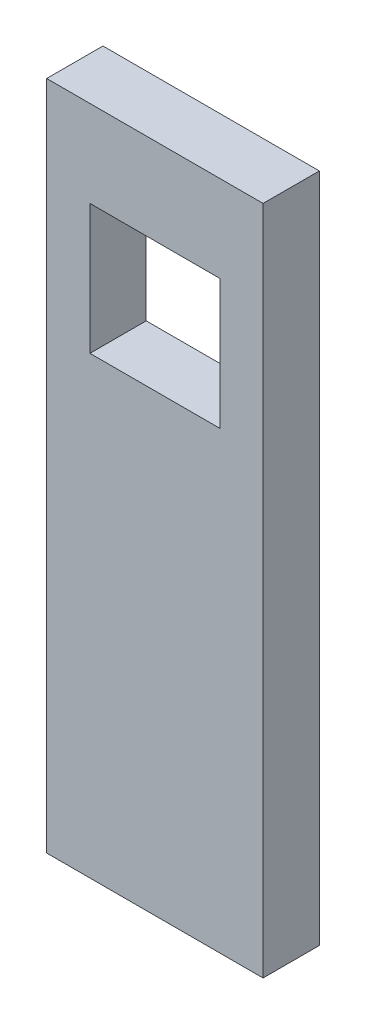
SolidWorks part; units mm, degrees
ref_plane "Front Plane" through (0, 0, 0) normal (0, 0, 1) x (1, 0, 0)
ref_plane "Top Plane" through (0, 0, 0) normal (0, 1, 0) x (1, 0, 0)
ref_plane "Right Plane" through (0, 0, 0) normal (1, 0, 0) x (0, 0, -1)
sketch "Sketch1" plane through (0, 0, 0) normal (0, 0, 1) x (1, 0, 0)
  line L0 (0, 62) -> (0, 42)
  line L1 (0, 62) -> (20, 62)
  line L2 (0, 42) -> (0, 37)
  line L3 (20, 0) -> (0, 0)
  line L4 (4, 54) -> (16, 54)
  line L5 (4, 42) -> (16, 42)
  line L6 (4, 54) -> (4, 42)
  line L7 (16, 54) -> (16, 42)
  line L8 (0, 42) -> (20, 42) construction
  line L9 (0, 37) -> (20, 37) construction
  line L10 (0, 37) -> (0, 25)
  line L11 (0, 25) -> (0, 20)
  line L12 (20, 42) -> (20, 37)
  line L13 (20, 62) -> (20, 42)
  line L14 (0, 20) -> (0, 0)
  line L15 (20, 37) -> (20, 25)
  line L16 (20, 25) -> (20, 20)
  line L17 (20, 20) -> (20, 0)
  line L18 (0, 25) -> (20, 25) construction
  line L19 (20, 20) -> (0, 20) construction
  line L20 (10, -0.0005) -> (10, 4.0956) construction
  point P18 (10, 42)
  point P20 (10, 54)
  point P21 (10, 62)
  dimension "D1" = 20
  dimension "D2" = 12
  dimension "D3" = 5
  dimension "D4" = 20
  dimension "D5" = 12
  dimension "D6" = 12
extrude "Boss-Extrude1" add sketch "Sketch1" along normal mid plane 5.2
